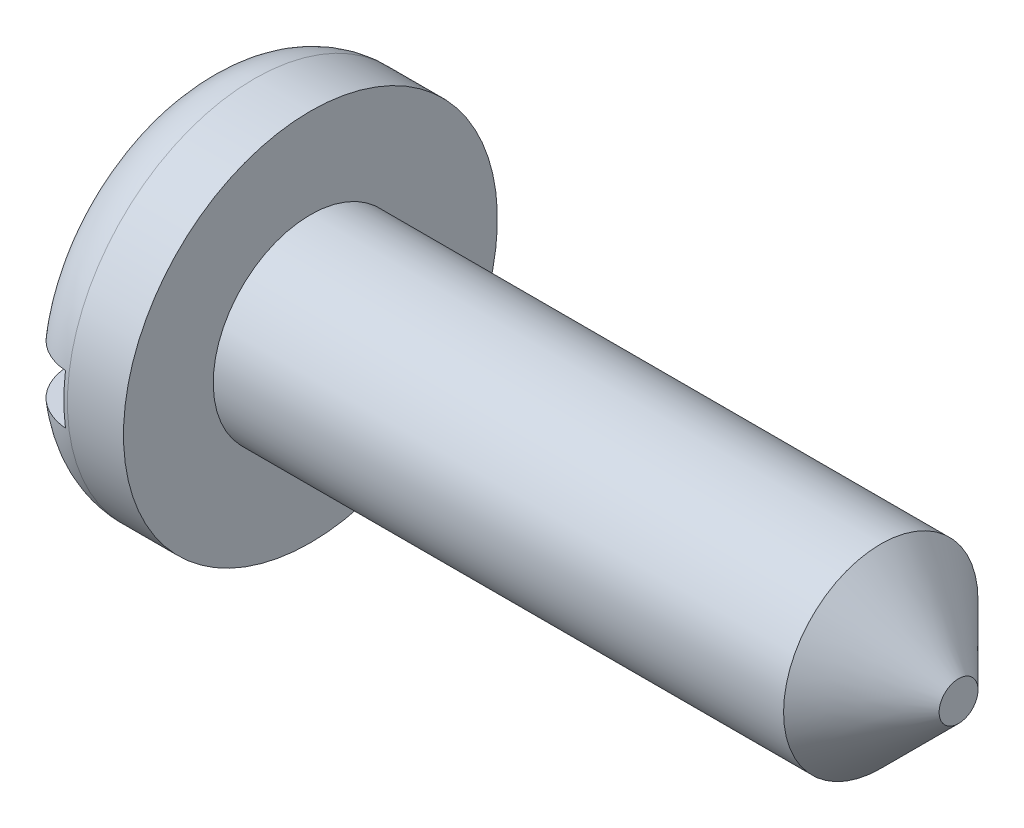
SolidWorks part; units mm, degrees
ref_plane "Front" through (0, 0, 0) normal (0, 0, 1) x (1, 0, 0)
ref_plane "Top" through (0, 0, 0) normal (0, 1, 0) x (1, 0, 0)
ref_plane "Right" through (0, 0, 0) normal (1, 0, 0) x (0, 0, -1)
ref_axis "Axis1" through (-84.4107, 0, 0) along (1, 0, 0)
ref_axis "Axis2" through (0, 64.3378, 0) along (0, -1, 0)
ref_axis "Axis3" through (0, 0, -102.329) along (0, 0, 1)
sketch "Sketch1" plane through (0, 0, 0) normal (0, 0, 1) x (1, 0, 0)
  line L0 (0, 0) -> (0, 2.625)
  line L1 (1.125, 3.75) -> (2.25, 3.75)
  line L2 (2.25, 3.75) -> (2.25, 1.95)
  line L3 (2.25, 1.95) -> (13.69, 1.95)
  line L4 (15.25, 0.39) -> (15.25, 0)
  line L5 (15.25, 0) -> (0, 0) construction
  line L6 (13.69, 1.95) -> (15.25, 0.39)
  line L7 (0, 0) -> (15.25, 0)
  arc A0 (0, 2.625) -> (1.125, 3.75) centre (1.125, 2.625) cw
  point P5 (15.25, 1.95)
  point P9 (0, 3.75)
  dimension "D3" = 1.125
  dimension "k" = 2.25
  dimension "L" = 13
  dimension "d2" = 7.5
  dimension "d1" = 3.9
revolve "Revolve1" add sketch "Sketch1" angle 360 about L5
sketch "Sketch2" plane through (0, 0, 0) normal (0, 0, 1) x (1, 0, 0)
  line L1 (0, 0.5) -> (1.05, 0.5)
  line L2 (0, 0.5) -> (0, -0.5)
  line L3 (0, -0.5) -> (1.05, -0.5)
  line L4 (1.05, 0.5) -> (1.05, -0.5)
  dimension "n" = 1
  dimension "t" = 1.05
extrude "Cut-Extrude1" cut sketch "Sketch2" against normal through all and the other way through all
equation "\"D3@Sketch1\" = \"k@Sketch1\"/2"
equation "\"D6@Sketch1\" = \"d1@Sketch1\"/2.5"
